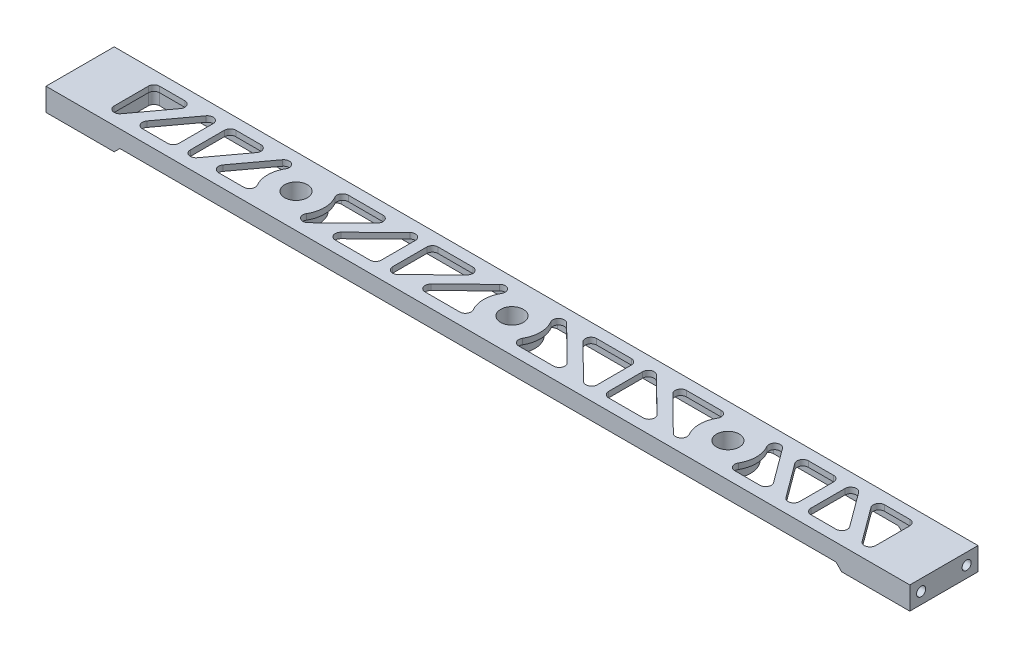
SolidWorks part; units mm, degrees
material "6061 Alloy"
ref_plane "Front Plane" through (0, 0, 0) normal (0, 0, 1) x (1, 0, 0)
ref_plane "Top Plane" through (0, 0, 0) normal (0, 1, 0) x (1, 0, 0)
ref_plane "Right Plane" through (0, 0, 0) normal (1, 0, 0) x (0, 0, -1)
sketch "Sketch1" plane through (0, 0, 0) normal (1, 0, 0) x (0, 0, -1)
  line L1 (-19.05, -6.35) -> (19.05, -6.35)
  line L2 (-19.05, -6.35) -> (-19.05, 6.35)
  line L3 (-19.05, 6.35) -> (19.05, 6.35)
  line L4 (19.05, -6.35) -> (19.05, 6.35)
  line L5 (-19.05, -6.35) -> (19.05, 6.35) construction
  line L6 (-19.05, 6.35) -> (19.05, -6.35) construction
  point P0 (0, 0)
  dimension "D1" = 38.1
  dimension "D2" = 12.7
extrude "Boss-Extrude1" add sketch "Sketch1" along normal mid plane 482.6
hole_wizard "1/4-20 Tapped Hole1" positions "3DSketch1" profile "Sketch3" tap size "1/4-20" standard "ANSI Inch"
sketch3d "3DSketch1"
  line L4 (241.3, 0, 19.05) -> (241.3, 0, 12.7) construction
  line L5 (241.3, 6.35, 19.05) -> (241.3, -6.35, 19.05) construction
  line L6 (241.3, 0, 12.7) -> (241.3, 0, -12.7) construction
  line L7 (241.3, 0, -12.7) -> (241.3, 0, -19.05) construction
  line L8 (241.3, -6.35, -19.05) -> (241.3, 6.35, -19.05) construction
  point P0 (241.3, 0, 12.7)
  point P2 (241.3, 0, -12.7)
  dimension "D1" = 25.4
sketch "Sketch3" plane through (241.3, 0, 12.7) normal (0, 1, 0) x (0, 0, -1)
  line L0 (0, 0) -> (0, 20.5838)
  line L1 (0, 20.5838) -> (2.5527, 19.05)
  line L2 (2.5527, 19.05) -> (2.5527, 0)
  line L5 (2.5527, 0) -> (0, 0)
  line L10 (0, 20.5838) -> (-2.5527, 19.05) construction
  line L11 (0, -6.35) -> (0, 107.95) construction
  dimension "Tap Drill Dia." = 5.1054
  dimension "Tap Drill Depth" = 19.05
  dimension "Drill Angle" = 118
sketch "Sketch2" plane through (0, 6.35, 0) normal (0, 1, 0) x (1, 0, 0)
  line L0 (0, 0) -> (241.3, 0) construction
  line L1 (241.3, -19.05) -> (241.3, 19.05) construction
  circle A0 centre (0, 0) radius 6.35
  circle A1 centre (120.65, 0) radius 6.35
  dimension "D1" = 12.7
extrude "Cut-Extrude1" cut sketch "Sketch2" against normal through all
sketch "Sketch4" plane through (0, -6.35, 0) normal (0, -1, 0) x (1, 0, 0)
  line L1 (9.525, 15.875) -> (111.125, 15.875)
  line L2 (130.175, 15.875) -> (212.725, 15.875)
  line L3 (215.9, 12.7) -> (215.9, -12.7)
  line L4 (212.725, -15.875) -> (130.175, -15.875)
  line L5 (111.125, -15.875) -> (9.525, -15.875)
  line L6 (241.3, 0) -> (215.9, 0) construction
  line L8 (241.3, 19.05) -> (241.3, -19.05) construction
  line L9 (241.3, 19.05) -> (-241.3, 19.05) construction
  arc A0 (7.62, -10.16) -> (7.62, 10.16) centre (0, 0) ccw
  arc A1 (113.03, 10.16) -> (113.03, -10.16) centre (120.65, 0) ccw
  arc A2 (128.27, 10.16) -> (128.27, -10.16) centre (120.65, 0) cw
  arc A3 (128.27, 10.16) -> (130.175, 15.875) centre (130.175, 12.7) cw
  arc A4 (128.27, -10.16) -> (130.175, -15.875) centre (130.175, -12.7) ccw
  arc A5 (113.03, -10.16) -> (111.125, -15.875) centre (111.125, -12.7) cw
  arc A6 (215.9, -12.7) -> (212.725, -15.875) centre (212.725, -12.7) cw
  arc A7 (212.725, 15.875) -> (215.9, 12.7) centre (212.725, 12.7) cw
  arc A8 (7.62, -10.16) -> (9.525, -15.875) centre (9.525, -12.7) ccw
  arc A9 (7.62, 10.16) -> (9.525, 15.875) centre (9.525, 12.7) cw
  arc A10 (113.03, 10.16) -> (111.125, 15.875) centre (111.125, 12.7) ccw
  dimension "D3" = 25.4
  dimension "D4" = 3.175
  dimension "D1" = 12.7
  dimension "D2" = 3.175
extrude "Cut-Extrude2" cut sketch "Sketch4" against normal blind 9.525
mirror "Mirror2" about plane through (0, 0, 0) normal (1, 0, 0) of "Cut-Extrude2", "Cut-Extrude1", "1/4-20 Tapped Hole1"
sketch "Sketch5" plane through (0, 3.175, 0) normal (0, -1, 0) x (1, 0, 0)
  line L0 (0, 19.05) -> (0, -19.05) construction
  line L1 (241.3, 19.05) -> (-241.3, 19.05) construction
  line L2 (241.3, -19.05) -> (-241.3, -19.05) construction
  line L3 (-212.725, 9.525) -> (-212.725, -9.525)
  line L4 (-209.55, -12.7) -> (-195.4852, -12.7)
  line L5 (-192.931, -7.6392) -> (-206.9957, 11.4108)
  line L6 (-193.7636, 12.7) -> (-179.6989, 12.7)
  line L7 (-176.5239, 9.525) -> (-176.5239, -9.525)
  line L8 (-182.2532, -11.4108) -> (-196.3179, 7.6392)
  line L11 (-212.725, 0) -> (-215.9, 0) construction
  line L12 (-215.9, -12.7) -> (-215.9, 12.7) construction
  line L13 (-186.7313, 12.7) -> (-186.7313, 15.875) construction
  line L14 (-202.5176, -12.7) -> (-202.5176, -15.875) construction
  line L15 (-130.175, -15.875) -> (-212.725, -15.875) construction
  line L16 (-212.725, 15.875) -> (-130.175, 15.875) construction
  line L17 (-199.9634, 1.8858) -> (-194.8548, 5.6575) construction
  line L18 (-170.1739, 9.525) -> (-170.1739, -9.525)
  line L19 (-166.9989, -12.7) -> (-152.9341, -12.7)
  line L21 (-150.3799, -7.6392) -> (-164.4446, 11.4108)
  line L22 (-176.5239, 0) -> (-170.1739, 0) construction
  line L23 (-136.525, 0) -> (-133.35, 0) construction
  line L25 (-151.2125, 12.7) -> (-137.1478, 12.7)
  line L26 (-153.7668, 7.6392) -> (-139.702, -11.4108)
  line L27 (-157.4122, 1.8858) -> (-152.3037, 5.6575) construction
  line L28 (-104.1522, -12.7) -> (-84.7855, -12.7)
  line L29 (-82.559, -7.2615) -> (-101.9257, 11.7885)
  line L30 (-86.0418, 12.7) -> (-66.675, 12.7)
  line L32 (-63.5, 9.525) -> (-63.5, -9.525)
  line L33 (-68.9015, -11.7885) -> (-88.2682, 7.2615)
  line L34 (-107.95, 0) -> (-104.775, 0) construction
  line L35 (-92.2424, 2.2635) -> (-87.7894, 6.7905) construction
  line L36 (-15.875, 0) -> (-12.7, 0) construction
  line L37 (-57.15, 9.525) -> (-57.15, -9.525)
  line L38 (-53.975, -12.7) -> (-34.6082, -12.7)
  line L39 (-32.3818, -7.2615) -> (-51.7485, 11.7885)
  line L40 (-38.091, 7.2615) -> (-18.7243, -11.7885)
  line L41 (-35.8645, 12.7) -> (-16.4978, 12.7)
  line L42 (-63.5, 0) -> (-57.15, 0) construction
  line L43 (-42.0651, 2.2635) -> (-37.6122, 6.7905) construction
  arc A0 (-193.7636, 12.7) -> (-196.3179, 7.6392) centre (-193.7636, 9.525) ccw
  arc A1 (-179.6989, 12.7) -> (-176.5239, 9.525) centre (-179.6989, 9.525) cw
  arc A2 (-176.5239, -9.525) -> (-182.2532, -11.4108) centre (-179.6989, -9.525) cw
  arc A3 (-195.4852, -12.7) -> (-192.931, -7.6392) centre (-195.4852, -9.525) ccw
  arc A4 (-212.725, -9.525) -> (-209.55, -12.7) centre (-209.55, -9.525) ccw
  arc A5 (-212.725, 9.525) -> (-206.9957, 11.4108) centre (-209.55, 9.525) cw
  arc A6 (-152.9341, -12.7) -> (-150.3799, -7.6392) centre (-152.9341, -9.525) ccw
  arc A7 (-170.1739, -9.525) -> (-166.9989, -12.7) centre (-166.9989, -9.525) ccw
  arc A11 (-170.1739, 9.525) -> (-164.4446, 11.4108) centre (-166.9989, 9.525) cw
  arc A12 (-134.3982, 7.9375) -> (-134.3982, -7.9375) centre (-120.65, 0) ccw
  arc A13 (-128.27, 10.16) -> (-128.27, -10.16) centre (-120.65, 0) ccw construction
  arc A14 (-151.2125, 12.7) -> (-153.7668, 7.6392) centre (-151.2125, 9.525) ccw
  arc A16 (-137.1478, 12.7) -> (-134.3982, 7.9375) centre (-137.1478, 9.525) cw
  arc A17 (-134.3982, -7.9375) -> (-139.702, -11.4108) centre (-137.1478, -9.525) cw
  arc A18 (-106.9018, -7.9375) -> (-106.9018, 7.9375) centre (-120.65, 0) ccw
  arc A19 (-84.7855, -12.7) -> (-82.559, -7.2615) centre (-84.7855, -9.525) ccw
  arc A20 (-63.5, -9.525) -> (-68.9015, -11.7885) centre (-66.675, -9.525) cw
  arc A22 (-66.675, 12.7) -> (-63.5, 9.525) centre (-66.675, 9.525) cw
  arc A23 (-86.0418, 12.7) -> (-88.2682, 7.2615) centre (-86.0418, 9.525) ccw
  arc A25 (-113.03, -10.16) -> (-113.03, 10.16) centre (-120.65, 0) ccw construction
  arc A27 (-106.9018, 7.9375) -> (-101.9257, 11.7885) centre (-104.1522, 9.525) cw
  arc A28 (-106.9018, -7.9375) -> (-104.1522, -12.7) centre (-104.1522, -9.525) ccw
  arc A29 (-13.7482, 7.9375) -> (-13.7482, -7.9375) centre (0, 0) ccw
  arc A31 (-7.62, 10.16) -> (-7.62, -10.16) centre (0, 0) ccw construction
  arc A32 (-13.7482, -7.9375) -> (-18.7243, -11.7885) centre (-16.4978, -9.525) cw
  arc A34 (-13.7482, 7.9375) -> (-16.4978, 12.7) centre (-16.4978, 9.525) ccw
  arc A35 (-38.091, 7.2615) -> (-35.8645, 12.7) centre (-35.8645, 9.525) cw
  arc A36 (-34.6082, -12.7) -> (-32.3818, -7.2615) centre (-34.6082, -9.525) ccw
  arc A37 (-57.15, -9.525) -> (-53.975, -12.7) centre (-53.975, -9.525) ccw
  arc A38 (-57.15, 9.525) -> (-51.7485, 11.7885) centre (-53.975, 9.525) cw
  dimension "D1" = 3.175
  dimension "D2" = 3.175
  dimension "D3" = 6.35
extrude "Cut-Extrude3" cut sketch "Sketch5" against normal through all
mirror "Mirror3" about plane through (0, 0, 0) normal (1, 0, 0) of "Cut-Extrude3"
sketch "Sketch6" plane through (0, 0, -19.05) normal (0, 0, -1) x (-1, 0, 0)
  line L0 (0, 6.35) -> (0, -6.35) construction
  line L1 (-241.3, 6.35) -> (241.3, 6.35) construction
  line L2 (-241.3, -6.35) -> (241.3, -6.35) construction
  line L3 (-200.025, -3.175) -> (200.025, -3.175)
  line L4 (200.025, -3.175) -> (203.2, -6.35)
  line L5 (203.2, -6.35) -> (-203.2, -6.35)
  line L6 (-200.025, -3.175) -> (-203.2, -6.35)
  point P10 (0, -3.175)
  dimension "D1" = 3.175
  dimension "D2" = 38.1
  dimension "D3" = 45
extrude "Cut-Extrude4" cut sketch "Sketch6" against normal through all
